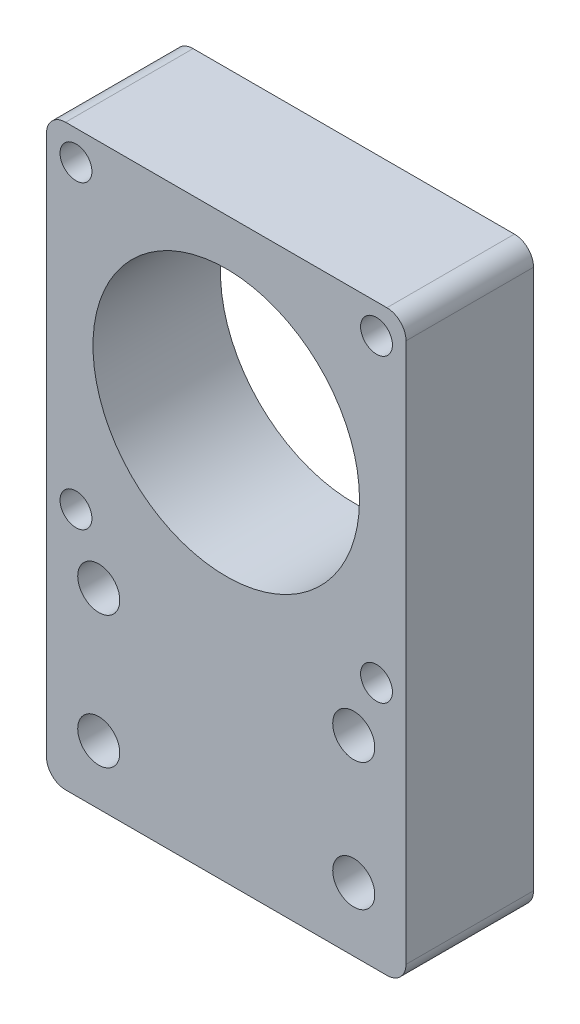
SolidWorks part; units mm, degrees
ref_plane "Front Plane" through (0, 0, 0) normal (0, 0, 1) x (1, 0, 0)
ref_plane "Top Plane" through (0, 0, 0) normal (0, 1, 0) x (1, 0, 0)
ref_plane "Right Plane" through (0, 0, 0) normal (1, 0, 0) x (0, 0, -1)
sketch "Sketch1" plane through (0, 0, 0) normal (0, 0, 1) x (1, 0, 0)
  line L4 (28.2, -3.2) -> (-28.2, -3.2)
  line L5 (28.2, 53.2) -> (28.2, -3.2)
  line L7 (-28.2, -3.2) -> (-28.2, 53.2)
  line L9 (-28.2, 53.2) -> (28.2, 53.2)
extrude "Boss-Extrude1" add sketch "Sketch1" along normal blind 20
sketch "Sketch2" plane through (0, 0, 20) normal (0, 0, 1) x (1, 0, 0)
  circle A3 centre (0, 25) radius 20.9044
extrude "Cut-Extrude2" cut sketch "Sketch2" against normal blind 20
sketch "Sketch3" plane through (0, 0, 0) normal (0, 0, -1) x (-1, 0, 0)
  line L0 (28.2, -3.2) -> (-28.2, -3.2) construction
  line L1 (-28.2, -3.2) -> (28.2, -3.2)
  line L2 (-28.2, -3.2) -> (-28.2, -37.5)
  line L3 (-28.2, -37.5) -> (28.2, -37.5)
  line L4 (28.2, -3.2) -> (28.2, -37.5)
  line L5 (-28.2, -3.2) -> (-28.2, 53.2) construction
  line L7 (-126, -17.5) -> (126, -17.5) construction
  dimension "D1" = 20
extrude "Boss-Extrude2" add sketch "Sketch3" against normal blind 20
fillet "Fillet1" radius 3 4 edges at (28.2, -37.5, 10) (-28.2, -37.5, 10) (28.2, 53.2, 10) (-28.2, 53.2, 10)
hole_wizard "Tap Drill for M6 Tap1" positions "Sketch4" profile "Sketch5" hole size "M6" standard "ISO" end condition through all
sketch "Sketch4" plane through (0, 0, 0) normal (0, 0, -1) x (-1, 0, 0)
  point P0 (-23.57, 48.57)
  point P2 (23.57, 48.57)
  point P4 (-23.57, 1.43)
  point P6 (23.57, 1.43)
sketch "Sketch5" plane through (23.57, 48.57, 0) normal (1, 0, 0) x (0, 1, 0)
  line L0 (0, 0) -> (0, 20)
  line L1 (0, 20) -> (2.5, 20)
  line L2 (2.5, 20) -> (2.5, 0)
  line L5 (2.5, 0) -> (0, 0)
  line L11 (0, -6.35) -> (0, 107.95) construction
  dimension "Thru Hole Dia." = 5
  dimension "Thru Hole Depth" = 20
hole_wizard "M6 Clearance Hole1" positions "Sketch6" profile "Sketch7" hole size "M6" standard "ISO" end condition through all
sketch "Sketch6" plane through (0, 0, 0) normal (0, 0, -1) x (-1, 0, 0)
  point P0 (-20, -7.5)
  point P2 (-20, -27.5)
  point P4 (20, -28.2377)
  point P6 (20, -7.5)
sketch "Sketch7" plane through (20, -7.5, 0) normal (1, 0, 0) x (0, 1, 0)
  line L0 (0, 0) -> (0, 20)
  line L1 (0, 20) -> (3.3, 20)
  line L2 (3.3, 20) -> (3.3, 0)
  line L5 (3.3, 0) -> (0, 0)
  line L11 (0, -6.35) -> (0, 107.95) construction
  dimension "Thru Hole Dia." = 6.6
  dimension "Thru Hole Depth" = 20
